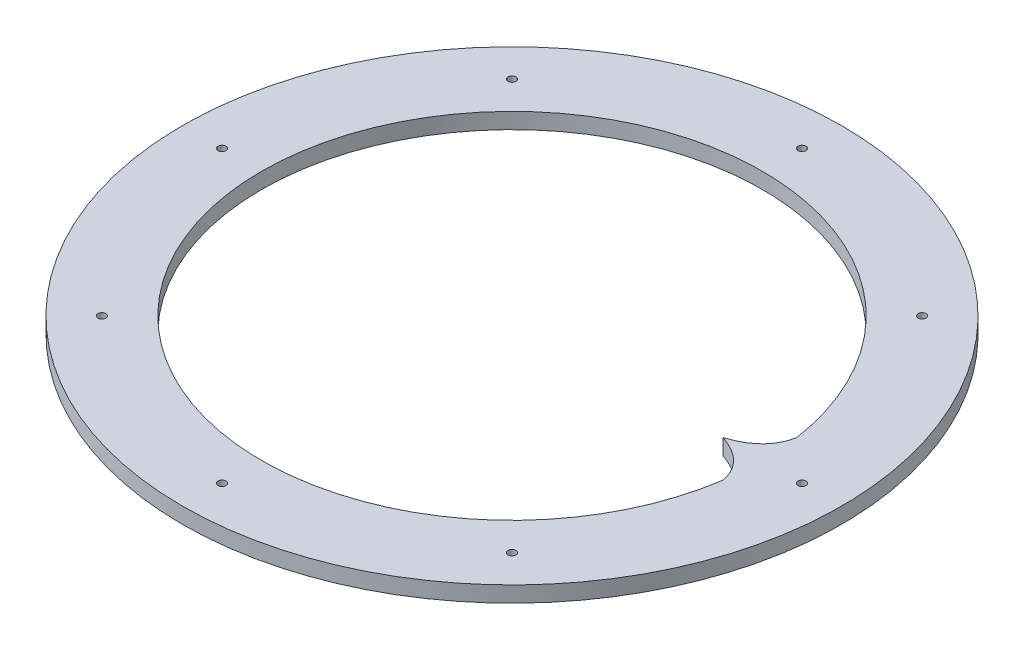
SolidWorks part; units mm, degrees
note: '?' marks a value the reader was unsure of.
ref_plane "Front Plane" through (0, 0, 0) normal (0, 0, 1) x (1, 0, 0)
ref_plane "Top Plane" through (0, 0, 0) normal (0, 1, 0) x (1, 0, 0)
ref_plane "Right Plane" through (0, 0, 0) normal (1, 0, 0) x (0, 0, -1)
sketch "Sketch1" plane through (0, 0, 0) normal (0, 1, 0) x (1, 0, 0)
  line L0 (-95, 0) -> (95, 0) construction
  line L1 (0, 95) -> (0, -95) construction
  line L2 (-67.1751, -67.1751) -> (67.1751, 67.1751) construction
  line L3 (-67.1751, 67.1751) -> (67.1751, -67.1751) construction
  line L4 (67.1751, -67.1751) -> (88.3883, -88.3883) construction
  line L5 (95, 0) -> (125, 0) construction
  line L6 (67.1751, 67.1751) -> (88.3883, 88.3883) construction
  line L7 (0, -95) -> (0, -125) construction
  line L8 (93.9765, 13.9075) -> (92.0728, 3.9574) construction
  line L9 (92.0728, 3.9574) -> (79.9987, 0) construction
  line L10 (93.9765, -13.9075) -> (92.0728, -3.9574) construction
  line L11 (92.0728, -3.9574) -> (79.9987, 0) construction
  arc A0 (93.9765, 13.9075) -> (93.9765, -13.9075) centre (0, 0) ccw
  circle A1 centre (0, 0) radius 125
  circle A2 centre (0, -110) radius 1.5
  circle A3 centre (77.7817, -77.7817) radius 1.5
  circle A4 centre (110, 0) radius 1.5
  circle A5 centre (77.7817, 77.7817) radius 1.5
  circle A6 centre (0, 110) radius 1.5
  circle A7 centre (-77.7817, 77.7817) radius 1.5
  circle A8 centre (-110, 0) radius 1.5
  circle A9 centre (-77.7817, -77.7817) radius 1.5
  spline S0 degree 2 poles (93.9765, 13.9075) (92.0728, 3.9574) (79.9987, 0) knots 0 0 0 1 1 1
  spline S1 degree 2 poles (93.9765, -13.9075) (92.0728, -3.9574) (79.9987, 0) knots 0 0 0 1 1 1
  point P11 (0, 0)
  point P14 (0, 0)
  dimension "D1" = 15
  dimension "D2" = 15
  dimension "D3" = 15
  dimension "D4" = 15
extrude "Boss-Extrude1" add sketch "Sketch1" along normal blind 6
convert to sheet metal "Convert-Solid1" [suppressed] bend radius? 10 thickness? 4.75
sketch "Bend-Lines1" [suppressed] plane through (0, 0, 0) normal (0, 1, 0) x (1, 0, 0)
sketch "Bounding-Box1" [suppressed] plane through (0, 0, 0) normal (0, 1, 0) x (1, 0, 0)
sheet metal parameters "Sheet-Metal2" thickness 4.75 parameters "D1"=10
flat pattern "Flat-Pattern2" [suppressed]
sketch "Bend-Lines2" plane through (0, 0, 0) normal (0, 1, 0) x (1, 0, 0)
sketch3d "Bounding-Box2" [suppressed]
  line L0 (-125.0764, 124.9235, 0) -> (-124.9234, -125.0764, 0) construction
  line L1 (124.9235, 125.0764, 0) -> (125.0764, -124.9235, 0) construction
  line L2 (-125.0764, 124.9235, 0) -> (124.9235, 125.0764, 0) construction
  line L3 (-124.9234, -125.0764, 0) -> (125.0764, -124.9235, 0) construction
